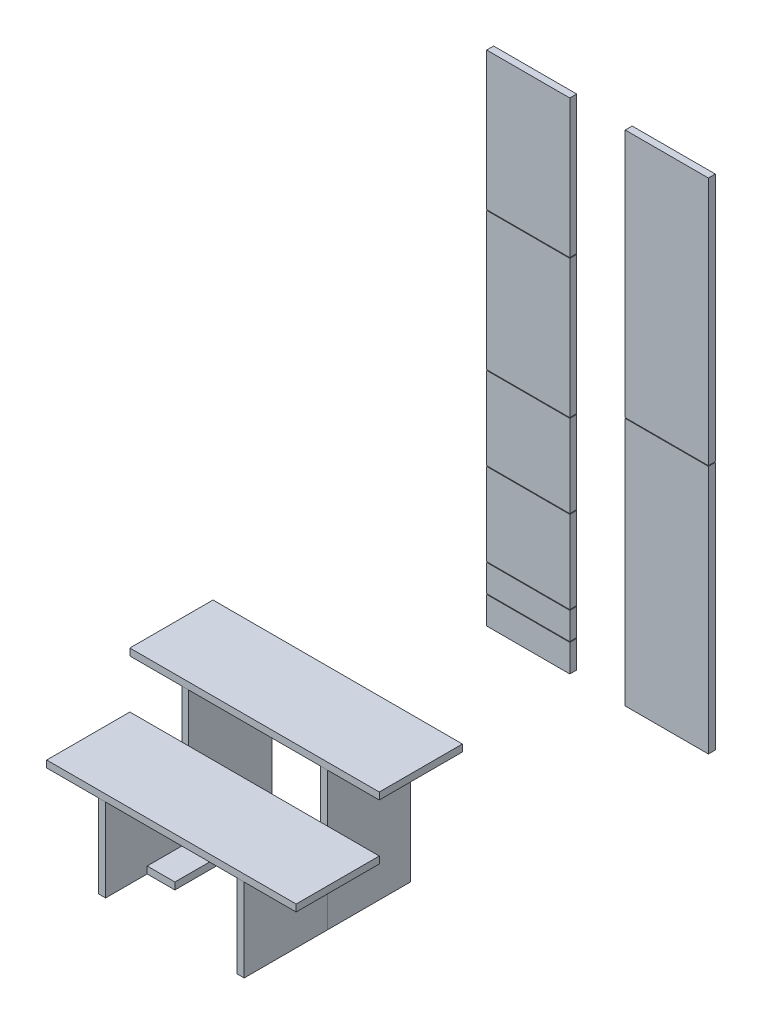
SolidWorks part; units mm, degrees
other "DetailItem1"
ref_plane "Front Plane" through (0, 0, 0) normal (0, 0, 1) x (1, 0, 0)
ref_plane "Top Plane" through (0, 0, 0) normal (0, 1, 0) x (1, 0, 0)
ref_plane "Right Plane" through (0, 0, 0) normal (1, 0, 0) x (0, 0, -1)
sketch "Sketch1" plane through (0, 0, 0) normal (0, 1, 0) x (1, 0, 0)
  line L0 (-254, 0) -> (254, 0) construction
  line L2 (-266.7, 152.4) -> (-241.3, 152.4)
  line L3 (-266.7, 152.4) -> (-266.7, -152.4)
  line L4 (-266.7, -152.4) -> (-241.3, -152.4)
  line L5 (-241.3, 152.4) -> (-241.3, -152.4)
  line L6 (-266.7, 152.4) -> (-241.3, -152.4) construction
  line L7 (-266.7, -152.4) -> (-241.3, 152.4) construction
  line L8 (241.3, 152.4) -> (266.7, 152.4)
  line L9 (241.3, 152.4) -> (241.3, -152.4)
  line L10 (241.3, -152.4) -> (266.7, -152.4)
  line L11 (266.7, 152.4) -> (266.7, -152.4)
  line L12 (241.3, 152.4) -> (266.7, -152.4) construction
  line L13 (241.3, -152.4) -> (266.7, 152.4) construction
  dimension "D1" = 25.4
  dimension "D2" = 304.8
  dimension "D3" = 508
extrude "Boss-Extrude1" add sketch "Sketch1" along normal blind 508
sketch "Sketch2" plane through (0, 508, 0) normal (0, 1, 0) x (1, 0, 0)
  line L0 (-241.3, 152.4) -> (-266.7, 152.4) construction
  line L1 (-457.2, -152.4) -> (457.2, -152.4)
  line L2 (-457.2, -152.4) -> (-457.2, 152.4)
  line L3 (-457.2, 152.4) -> (457.2, 152.4)
  line L4 (457.2, -152.4) -> (457.2, 152.4)
  line L5 (-457.2, -152.4) -> (457.2, 152.4) construction
  line L6 (-457.2, 152.4) -> (457.2, -152.4) construction
  point P0 (0, 0)
  dimension "D1" = 914.4
extrude "Boss-Extrude2" add sketch "Sketch2" along normal blind 25.4 separate body
sketch "Sketch3" plane through (0, 0, 0) normal (0, 1, 0) x (1, 0, 0)
  line L0 (-254, -304.8) -> (254, -304.8) construction
  line L1 (-457.2, -152.4) -> (457.2, -152.4) construction
  line L2 (-266.7, -152.4) -> (-241.3, -152.4)
  line L3 (-266.7, -152.4) -> (-266.7, -457.2)
  line L4 (-266.7, -457.2) -> (-241.3, -457.2)
  line L5 (-241.3, -152.4) -> (-241.3, -457.2)
  line L6 (-266.7, -152.4) -> (-241.3, -457.2) construction
  line L7 (-266.7, -457.2) -> (-241.3, -152.4) construction
  line L8 (241.3, -152.4) -> (266.7, -152.4)
  line L9 (241.3, -152.4) -> (241.3, -457.2)
  line L10 (241.3, -457.2) -> (266.7, -457.2)
  line L11 (266.7, -152.4) -> (266.7, -457.2)
  line L12 (241.3, -152.4) -> (266.7, -457.2) construction
  line L13 (241.3, -457.2) -> (266.7, -152.4) construction
  point P2 (0, -304.8)
  dimension "D1" = 25.4
  dimension "D2" = 304.8
  dimension "D3" = 508
extrude "Boss-Extrude3" add sketch "Sketch3" along normal blind 304.8 separate body
sketch "Sketch4" plane through (0, 304.8, 0) normal (0, 1, 0) x (1, 0, 0)
  line L0 (-457.2, -152.4) -> (457.2, -152.4) construction
  line L1 (-457.2, -457.2) -> (457.2, -457.2)
  line L2 (-457.2, -457.2) -> (-457.2, -152.4)
  line L3 (-457.2, -152.4) -> (457.2, -152.4)
  line L4 (457.2, -457.2) -> (457.2, -152.4)
  line L5 (-457.2, -457.2) -> (457.2, -152.4) construction
  line L6 (-457.2, -152.4) -> (457.2, -457.2) construction
  line L7 (-266.7, -457.2) -> (-241.3, -457.2) construction
  point P0 (0, -304.8)
  point P9 (0, 0)
  dimension "D1" = 914.4
extrude "Boss-Extrude4" add sketch "Sketch4" along normal blind 25.4 separate body
sketch "Sketch5" plane through (0, 0, 0) normal (0, 1, 0) x (1, 0, 0)
  line L0 (0, 0) -> (0, 1117.6) construction
  line L1 (-254, 1117.6) -> (254, 1117.6) construction
  line L3 (-406.4, 1130.3) -> (-101.6, 1130.3)
  line L4 (-406.4, 1130.3) -> (-406.4, 1104.9)
  line L5 (-406.4, 1104.9) -> (-101.6, 1104.9)
  line L6 (-101.6, 1130.3) -> (-101.6, 1104.9)
  line L7 (-406.4, 1130.3) -> (-101.6, 1104.9) construction
  line L8 (-406.4, 1104.9) -> (-101.6, 1130.3) construction
  line L9 (101.6, 1130.3) -> (406.4, 1130.3)
  line L10 (101.6, 1130.3) -> (101.6, 1104.9)
  line L11 (101.6, 1104.9) -> (406.4, 1104.9)
  line L12 (406.4, 1130.3) -> (406.4, 1104.9)
  line L13 (101.6, 1130.3) -> (406.4, 1104.9) construction
  line L14 (101.6, 1104.9) -> (406.4, 1130.3) construction
  point P5 (0, 1117.6)
  dimension "D1" = 25.4
  dimension "D2" = 304.8
  dimension "D3" = 25.4
  dimension "D4" = 304.8
  dimension "D5" = 1117.6
  dimension "D6" = 508
extrude "Boss-Extrude5" add sketch "Sketch5" along normal blind 1828.8 separate body
sketch "Sketch6" plane through (0, 0, -1130.3) normal (0, 0, -1) x (-1, 0, 0)
  line L0 (-406.4, 914.4) -> (-101.6, 914.4)
  line L1 (-406.4, 1828.8) -> (-406.4, 0) construction
  line L2 (-101.6, 1828.8) -> (-101.6, 0) construction
  line L3 (101.6, 1320.8) -> (406.4, 1320.8)
  line L4 (101.6, 1828.8) -> (101.6, 0) construction
  line L5 (406.4, 1828.8) -> (406.4, 0) construction
  line L6 (101.6, 812.8) -> (406.4, 812.8)
  line L7 (101.6, 508) -> (406.4, 508)
  line L8 (101.6, 203.2) -> (406.4, 203.2)
  line L9 (101.6, 101.6) -> (406.4, 101.6)
  line L10 (101.6, 1828.8) -> (406.4, 1828.8) construction
  line L11 (101.6, 0) -> (406.4, 0) construction
  dimension "D1" = 508
  dimension "D2" = 508
  dimension "D3" = 304.8
  dimension "D4" = 304.8
  dimension "D5" = 101.6
sketch "Sketch7" plane through (0, 0, 0) normal (0, -1, 0) x (1, 0, 0)
  line L0 (-241.3, 152.4) -> (241.3, 152.4) construction
  line L1 (241.3, -152.4) -> (241.3, 152.4) construction
  line L2 (-241.3, 304.8) -> (241.3, 304.8)
  line L3 (-241.3, 304.8) -> (-241.3, 0)
  line L4 (-241.3, 0) -> (241.3, 0)
  line L5 (241.3, 304.8) -> (241.3, 0)
  line L6 (-241.3, 304.8) -> (241.3, 0) construction
  line L7 (-241.3, 0) -> (241.3, 304.8) construction
  line L8 (-139.7, 304.8) -> (-139.7, 0)
  line L9 (139.7, 304.8) -> (139.7, 0)
  point P4 (0, 152.4)
  line M7 (-241.3, 152.4) -> (-241.3, 457.2)
  dimension "D1" = 304.8
  dimension "D2" = 101.6
  dimension "D3" = 101.6
extrude "Boss-Extrude6" add sketch "Sketch7" against normal blind 25.4 separate body contours L8 L2 L3 L4 M7 | L2 L9 L4 L5 region at (-190.5, 0, 152.4) region at (190.5, 0, 152.4)
extrude "Cut-Extrude-Thin1" cut sketch "Sketch6" against normal blind 25.4 thin thin type mid plane wall 2.54
equation "\"D3@Sketch1\"=36-16"
equation "\"D3@Sketch3\"=36-16"
